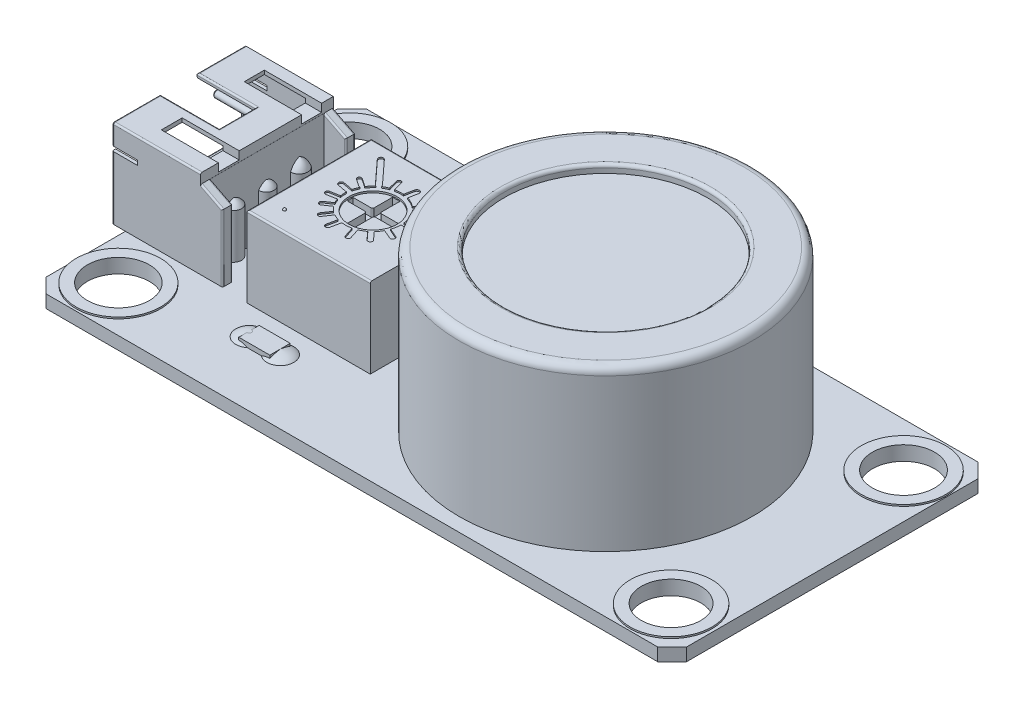
SolidWorks part; units mm, degrees
ref_plane "Alzado" through (0, 0, 0) normal (0, 0, 1) x (1, 0, 0)
ref_plane "Planta" through (0, 0, 0) normal (0, 1, 0) x (1, 0, 0)
ref_plane "Vista lateral" through (0, 0, 0) normal (1, 0, 0) x (0, 0, -1)
sketch "Croquis1" plane through (0, 0, 0) normal (0, 1, 0) x (1, 0, 0)
  line L1 (20, -10) -> (-20, -10)
  line L2 (20, -10) -> (20, 10)
  line L3 (20, 10) -> (-20, 10)
  line L4 (-20, -10) -> (-20, 10)
  line L5 (20, -10) -> (-20, 10) construction
  line L6 (20, 10) -> (-20, -10) construction
  point P0 (0, 0)
  dimension "D1" = 20
  dimension "D2" = 40
extrude "Saliente-Extruir1" add sketch "Croquis1" along normal blind 0.8
chamfer "Chaflán1" distance 0.9 angle 45 4 edges at (20, 0.4, 10) (20, 0.4, -10) (-20, 0.4, -10) (-20, 0.4, 10)
sketch "Croquis2" plane through (0, 0.8, 0) normal (0, 1, 0) x (1, 0, 0)
  circle A0 centre (-17.4865, 7.3544) radius 2.5635
  circle A1 centre (-17.4865, 7.3544) radius 1.8635
  dimension "D1" = 0.7
extrude "Saliente-Extruir2" add sketch "Croquis2" along normal blind 0.1
sketch "Croquis3" plane through (0, 0.8, 0) normal (0, 1, 0) x (1, 0, 0)
  circle A0 centre (-17.3437, -7.2372) radius 2.6343
  circle A2 centre (-17.3437, -7.2372) radius 1.9343
  dimension "D2" = 0.7
extrude "Saliente-Extruir3" add sketch "Croquis3" along normal blind 0.1
sketch "Croquis4" plane through (0, 0.8, 0) normal (0, 1, 0) x (1, 0, 0)
  circle A0 centre (-17.4865, 7.3544) radius 1.8635
extrude "Cortar-Extruir1" cut sketch "Croquis4" against normal through all
sketch "Croquis5" plane through (0, 0.8, 0) normal (0, 1, 0) x (1, 0, 0)
  circle A0 centre (-17.3437, -7.2372) radius 1.9343
extrude "Cortar-Extruir2" cut sketch "Croquis5" against normal through all
sketch "Croquis6" plane through (0, 0.8, 0) normal (0, 1, 0) x (1, 0, 0)
  circle A0 centre (17.306, 7.1429) radius 2.6397
  circle A1 centre (17.306, 7.1429) radius 1.9397
  dimension "D1" = 0.7
extrude "Saliente-Extruir4" add sketch "Croquis6" along normal blind 0.1
sketch "Croquis7" plane through (0, 0.8, 0) normal (0, 1, 0) x (1, 0, 0)
  circle A0 centre (17.306, 7.1429) radius 1.9397
extrude "Cortar-Extruir3" cut sketch "Croquis7" against normal through all
sketch "Croquis8" plane through (0, 0.8, 0) normal (0, 1, 0) x (1, 0, 0)
  circle A0 centre (17.2585, -7.3247) radius 2.5546
  circle A1 centre (17.2585, -7.3247) radius 1.8546
  dimension "D1" = 0.7
extrude "Saliente-Extruir5" add sketch "Croquis8" along normal blind 0.1
sketch "Croquis9" plane through (0, 0.8, 0) normal (0, 1, 0) x (1, 0, 0)
  circle A0 centre (17.2585, -7.3247) radius 1.8546
extrude "Cortar-Extruir4" cut sketch "Croquis9" against normal through all
sketch "Croquis10" plane through (0, 0.8, 0) normal (0, 1, 0) x (1, 0, 0)
  circle A0 centre (5.8533, 0) radius 9.1478
extrude "Saliente-Extruir6" add sketch "Croquis10" along normal blind 10
fillet "Redondeo1" radius 0.5 1 edges at (5.8533, 10.8, 9.1478)
sketch "Croquis11" plane through (0, 10.8, 0) normal (0, 1, 0) x (1, 0, 0)
  circle A1 centre (5.8533, 0) radius 6.3478
extrude "Cortar-Extruir5" cut sketch "Croquis11" against normal blind 0.5
fillet "Redondeo2" radius 0.2 1 edges at (5.8533, 10.8, 6.3478)
sketch "Croquis12" plane through (0, 0.8, 0) normal (0, 1, 0) x (1, 0, 0)
  line L1 (-4.6304, -4.2212) -> (-12.3417, -4.2212)
  line L2 (-4.6304, -4.2212) -> (-4.6304, 3.5532)
  line L3 (-4.6304, 3.5532) -> (-12.3417, 3.5532)
  line L4 (-12.3417, -4.2212) -> (-12.3417, 3.5532)
  line L5 (-4.6304, -4.2212) -> (-12.3417, 3.5532) construction
  line L6 (-4.6304, 3.5532) -> (-12.3417, -4.2212) construction
  point P0 (-8.486, -0.334)
extrude "Saliente-Extruir7" add sketch "Croquis12" along normal blind 5
sketch "Croquis13" plane through (-12.3417, 0, 0) normal (-1, 0, 0) x (0, 0, 1)
  line L0 (-3.2482, 0.8) -> (-3.2482, 5.4444)
  line L1 (-3.5532, 0.8) -> (4.2212, 0.8) construction
  line L2 (-3.2482, 5.4444) -> (-2.7609, 5.4444)
  line L3 (-2.7609, 5.4444) -> (-2.7609, 0.8)
  line L4 (-3.2482, 0.8) -> (-2.7609, 0.8)
  line L5 (-0.2703, 0.8) -> (-0.2703, 5.4444)
  line L6 (-0.2703, 5.4444) -> (0.334, 5.4444)
  line L7 (0.334, 5.4444) -> (0.334, 0.8)
  line L8 (0.334, 0.8) -> (-0.2703, 0.8)
  line L9 (3.8446, 0.8) -> (3.8446, 5.4444)
  line L10 (3.8446, 5.4444) -> (3.213, 5.4444)
  line L11 (3.213, 5.4444) -> (3.213, 0.8)
  line L12 (3.213, 0.8) -> (3.8446, 0.8)
extrude "Cortar-Extruir6" cut sketch "Croquis13" against normal blind 0.5
sketch "Croquis14" plane through (-12.3417, 0, 0) normal (-1, 0, 0) x (0, 0, 1)
  line L0 (0.5209, 0.8) -> (0.5209, 5.4292)
  line L1 (0.334, 0.8) -> (3.213, 0.8) construction
  line L2 (0.5209, 5.4292) -> (0.6837, 5.4292)
  line L3 (0.6837, 5.4292) -> (0.6837, 0.8)
  line L4 (0.6837, 0.8) -> (0.5209, 0.8)
extrude "Cortar-Extruir7" cut sketch "Croquis14" against normal blind 0.5
sketch "Croquis15" plane through (0, 5.8, 0) normal (0, 1, 0) x (1, 0, 0)
  circle A0 centre (-8.486, -0.1934) radius 1.5
  dimension "D1" = 3
extrude "Cortar-Extruir8" cut sketch "Croquis15" against normal blind 0.2
sketch "Croquis16" plane through (0, 5.6, 0) normal (0, 1, 0) x (1, 0, 0)
  line L1 (-8.6131, -1.6051) -> (-8.2995, -1.6051)
  line L3 (-8.2995, 1.2424) -> (-8.6131, 1.2424)
  line L5 (-7.0615, -0.0779) -> (-7.0615, -0.3129)
  line L7 (-9.9142, -0.3129) -> (-9.9142, -0.0779)
  line L12 (-9.9142, -0.0779) -> (-9.9142, 0)
  line L13 (-9.9142, 0) -> (-8.7038, 0)
  line L14 (-8.7038, 0) -> (-8.7038, 1.2424)
  line L15 (-8.6131, 1.2424) -> (-8.7038, 1.2424)
  line L16 (-8.2995, 1.2424) -> (-8.248, 1.2424)
  line L17 (-8.248, 1.2424) -> (-8.248, 0)
  line L18 (-8.248, 0) -> (-7.0615, 0)
  line L19 (-7.0615, 0) -> (-7.0615, -0.0779)
  line L20 (-8.7038, -0.3729) -> (-8.7038, -1.6051)
  line L21 (-8.7038, -1.6051) -> (-8.6131, -1.6051)
  line L22 (-8.2995, -1.6051) -> (-8.248, -1.6051)
  line L23 (-8.248, -1.6051) -> (-8.248, -0.3729)
  line L24 (-9.9142, -0.3129) -> (-9.9142, -0.3729)
  line L25 (-9.9142, -0.3729) -> (-8.7038, -0.3729)
  line L26 (-7.0615, -0.3129) -> (-7.0615, -0.3729)
  line L27 (-7.0615, -0.3729) -> (-8.248, -0.3729)
extrude "Cortar-Extruir9" cut sketch "Croquis16" against normal blind 0.5
sketch "Croquis17" plane through (0, 5.8, 0) normal (0, 1, 0) x (1, 0, 0)
  line L0 (-6.7524, 0) -> (-5.2555, 0)
  line L2 (-5.249, -0.1934) -> (-6.7416, -0.1934)
  line L3 (-6.8257, -0.7476) -> (-6.2758, -0.9833)
  line L4 (-6.9397, -1.0137) -> (-6.3898, -1.2494)
  line L5 (-8.707, -1.9297) -> (-8.8384, -2.5488)
  line L6 (-8.989, -1.8699) -> (-9.1203, -2.489)
  line L8 (-9.3492, -1.7159) -> (-9.6944, -2.2236)
  line L9 (-7.2099, -1.3914) -> (-6.7759, -1.8719)
  line L10 (-7.4236, -1.5844) -> (-6.9895, -2.0649)
  line L11 (-9.5844, -1.5561) -> (-9.9295, -2.0638)
  line L12 (-7.819, -1.8113) -> (-7.6193, -2.4331)
  line L13 (-8.0863, -1.8972) -> (-7.8866, -2.5189)
  line L15 (-9.8499, -1.2901) -> (-10.3142, -1.6052)
  line L16 (-10.0091, -1.0555) -> (-10.4734, -1.3706)
  line L18 (-6.9446, 0.6958) -> (-6.5446, 0.8736)
  line L19 (-6.8207, 0.4171) -> (-6.4207, 0.5949)
  line L21 (-7.3525, 1.1956) -> (-6.9697, 1.5416)
  line L22 (-7.1786, 1.0031) -> (-6.7957, 1.3491)
  line L24 (-10.1981, -0.7928) -> (-10.742, -0.8882)
  line L25 (-10.2482, -0.507) -> (-10.7921, -0.6024)
  line L27 (-10.2774, -0.1035) -> (-10.8548, 0.0057)
  line L28 (-10.2191, 0.2045) -> (-10.7965, 0.3137)
  line L30 (-10.1497, 0.5884) -> (-10.6088, 0.8957)
  line L31 (-10.0059, 0.8032) -> (-10.465, 1.1105)
  line L33 (-9.6996, 1.1667) -> (-11.036, 2.6242)
  line L34 (-9.4691, 1.378) -> (-10.8056, 2.8355)
  line L36 (-9.1158, 1.5096) -> (-9.2471, 2.0302)
  line L37 (-8.8621, 1.5736) -> (-8.9935, 2.0942)
  line L39 (-8.3111, 1.5825) -> (-8.2061, 2.1257)
  line L40 (-7.9859, 1.5196) -> (-7.8808, 2.0628)
  arc A0 (-6.7524, 0) -> (-6.8485, 0.4078) centre (-8.486, -0.1934) ccw
  arc A1 (-5.249, -0.1934) -> (-5.2555, 0) centre (-5.2319, -0.096) ccw
  circle A2 centre (-8.486, -0.1934) radius 1.5
  arc A3 (-6.8257, -0.7476) -> (-6.8312, -0.7453) centre (-6.8827, -0.8806) ccw
  arc A4 (-6.3898, -1.2494) -> (-6.2758, -0.9833) centre (-6.3328, -1.1163) ccw
  arc A5 (-7.8208, -1.806) -> (-7.4274, -1.5799) centre (-8.486, -0.1934) ccw
  arc A6 (-7.214, -1.3871) -> (-6.9452, -1.0112) centre (-8.486, -0.1934) ccw
  arc A7 (-7.2099, -1.3914) -> (-7.214, -1.3871) centre (-7.3167, -1.4879) ccw
  arc A8 (-6.9895, -2.0649) -> (-6.7759, -1.8719) centre (-6.8827, -1.9684) ccw
  arc A9 (-7.819, -1.8113) -> (-7.8208, -1.806) centre (-7.9527, -1.8542) ccw
  arc A10 (-7.8866, -2.5189) -> (-7.6193, -2.4331) centre (-7.753, -2.476) ccw
  arc A11 (-8.0879, -1.8918) -> (-8.0863, -1.8972) centre (-7.9527, -1.8542) ccw
  arc A12 (-7.4274, -1.5799) -> (-7.4236, -1.5844) centre (-7.3167, -1.4879) ccw
  arc A13 (-6.9452, -1.0112) -> (-6.9397, -1.0137) centre (-6.8827, -0.8806) ccw
  arc A14 (-6.8312, -0.7453) -> (-6.7416, -0.1934) centre (-8.486, -0.1934) ccw
  arc A15 (-8.707, -1.9297) -> (-8.7059, -1.9239) centre (-8.848, -1.8998) ccw
  arc A16 (-9.1203, -2.489) -> (-8.8384, -2.5488) centre (-8.9793, -2.5189) ccw
  arc A17 (-9.3492, -1.7159) -> (-9.346, -1.7111) centre (-9.4668, -1.636) ccw
  arc A18 (-9.9295, -2.0638) -> (-9.6944, -2.2236) centre (-9.8119, -2.1437) ccw
  arc A19 (-9.8499, -1.2901) -> (-9.8452, -1.2868) centre (-9.9295, -1.1728) ccw
  arc A20 (-10.4734, -1.3706) -> (-10.3142, -1.6052) centre (-10.3938, -1.4879) ccw
  arc A21 (-6.9446, 0.6958) -> (-6.9748, 0.678) centre (-6.8827, 0.5564) ccw
  arc A22 (-6.4207, 0.5949) -> (-6.5446, 0.8736) centre (-6.4826, 0.7343) ccw
  arc A23 (-7.3525, 1.1956) -> (-7.3817, 1.157) centre (-7.2655, 1.0994) ccw
  arc A24 (-6.7957, 1.3491) -> (-6.9697, 1.5416) centre (-6.8827, 1.4454) ccw
  arc A25 (-10.1981, -0.7928) -> (-10.1343, -0.7646) centre (-10.2232, -0.6499) ccw
  arc A26 (-10.7921, -0.6024) -> (-10.742, -0.8882) centre (-10.7671, -0.7453) ccw
  arc A27 (-10.2774, -0.1035) -> (-10.2282, -0.105) centre (-10.2482, 0.0505) ccw
  arc A28 (-10.7965, 0.3137) -> (-10.8548, 0.0057) centre (-10.8256, 0.1597) ccw
  arc A29 (-10.1497, 0.5884) -> (-10.0553, 0.5686) centre (-10.0778, 0.6958) ccw
  arc A30 (-10.465, 1.1105) -> (-10.6088, 0.8957) centre (-10.5369, 1.0031) ccw
  arc A31 (-9.6996, 1.1667) -> (-9.6306, 1.123) centre (-9.5844, 1.2724) ccw
  arc A32 (-10.8056, 2.8355) -> (-11.036, 2.6242) centre (-10.9208, 2.7299) ccw
  arc A33 (-9.1158, 1.5096) -> (-9.0794, 1.4471) centre (-8.989, 1.5416) ccw
  arc A34 (-8.9935, 2.0942) -> (-9.2471, 2.0302) centre (-9.1203, 2.0622) ccw
  arc A35 (-8.3111, 1.5825) -> (-8.3139, 1.5425) centre (-8.1485, 1.5511) ccw
  arc A36 (-7.8808, 2.0628) -> (-8.2061, 2.1257) centre (-8.0435, 2.0942) ccw
  arc A37 (-6.8485, 0.4078) -> (-6.8207, 0.4171) centre (-6.8827, 0.5564) ccw
  arc A38 (-6.9748, 0.678) -> (-7.2013, 0.9867) centre (-8.486, -0.1934) ccw
  arc A39 (-7.2013, 0.9867) -> (-7.1786, 1.0031) centre (-7.2655, 1.0994) ccw
  arc A40 (-7.3817, 1.157) -> (-7.9982, 1.4815) centre (-8.486, -0.1934) ccw
  arc A41 (-7.9982, 1.4815) -> (-7.9859, 1.5196) centre (-8.1485, 1.5511) ccw
  arc A42 (-8.3139, 1.5425) -> (-8.862, 1.5101) centre (-8.486, -0.1934) ccw
  arc A43 (-8.862, 1.5101) -> (-8.8621, 1.5736) centre (-8.989, 1.5416) ccw
  arc A44 (-9.0794, 1.4471) -> (-9.4281, 1.2748) centre (-8.486, -0.1934) ccw
  arc A45 (-9.4281, 1.2748) -> (-9.4691, 1.378) centre (-9.5844, 1.2724) ccw
  arc A46 (-9.6306, 1.123) -> (-9.9576, 0.7434) centre (-8.486, -0.1934) ccw
  arc A47 (-9.9576, 0.7434) -> (-10.0059, 0.8032) centre (-10.0778, 0.6958) ccw
  arc A48 (-10.0553, 0.5686) -> (-10.1868, 0.1947) centre (-8.486, -0.1934) ccw
  arc A49 (-10.1868, 0.1947) -> (-10.2191, 0.2045) centre (-10.2482, 0.0505) ccw
  arc A50 (-10.2282, -0.105) -> (-10.2021, -0.5064) centre (-8.486, -0.1934) ccw
  arc A51 (-10.2021, -0.5064) -> (-10.2482, -0.507) centre (-10.2232, -0.6499) ccw
  arc A52 (-10.1343, -0.7646) -> (-10.0043, -1.0524) centre (-8.486, -0.1934) ccw
  arc A53 (-10.0043, -1.0524) -> (-10.0091, -1.0555) centre (-9.9295, -1.1728) ccw
  arc A54 (-9.8452, -1.2868) -> (-9.581, -1.5513) centre (-8.486, -0.1934) ccw
  arc A55 (-9.581, -1.5513) -> (-9.5844, -1.5561) centre (-9.4668, -1.636) ccw
  arc A56 (-9.346, -1.7111) -> (-8.9876, -1.8641) centre (-8.486, -0.1934) ccw
  arc A57 (-8.9876, -1.8641) -> (-8.989, -1.8699) centre (-8.848, -1.8998) ccw
  arc A58 (-8.7059, -1.9239) -> (-8.0879, -1.8918) centre (-8.486, -0.1934) ccw
  point P11 (-6.6078, -0.9985)
  point P18 (2.9909, -1.5468)
  point P19 (-8.9137, -2.2094)
  point P25 (-7.0997, -1.7281)
  point P32 (-7.8528, -2.1651)
  point P46 (-9.6394, -1.8898)
  point P53 (-10.1617, -1.3304)
  point P60 (-6.6827, 0.6453)
  point P67 (-7.0741, 1.2724)
  point P74 (-10.4951, -0.6976)
  point P81 (-10.5369, 0.1051)
  point P88 (-10.3074, 0.8495)
  point P95 (-10.2526, 2.0011)
  point P102 (-9.0546, 1.8019)
  point P109 (-8.096, 1.8226)
extrude "Cortar-Extruir10" cut sketch "Croquis17" against normal blind 0.09
fillet "Redondeo3" radius 0.1 3 edges at (-8.486, 5.8, -3.5532) (-12.3417, 5.8, 0.334) (-8.486, 5.8, 4.2212)
fillet "Redondeo4" radius 0.1 4 edges at (-8.7038, 5.35, 0.3729) (-8.248, 5.35, 0.3729) (-8.7038, 5.35, 0) (-8.248, 5.35, 0)
sketch "Croquis18" plane through (0, 5.8, 0) normal (0, 1, 0) x (1, 0, 0)
  line L0 (-11.2871, -3.0045) -> (-11.1022, -3.0045)
  arc A0 (-11.1022, -3.0045) -> (-11.2871, -3.0045) centre (-11.1947, -3.0045) ccw
revolve "Revolución1" add sketch "Croquis18" angle 360 about L0
sketch "Croquis19" plane through (0, 0.8, 0) normal (0, 1, 0) x (1, 0, 0)
  line L1 (-8.4965, -6.6295) -> (-10.4343, -6.6295)
  line L2 (-8.4965, -6.6295) -> (-8.4965, -5.3534)
  line L3 (-8.4965, -5.3534) -> (-10.4343, -5.3534)
  line L4 (-10.4343, -6.6295) -> (-10.4343, -5.3534)
  line L5 (-8.4965, -6.6295) -> (-10.4343, -5.3534) construction
  line L6 (-8.4965, -5.3534) -> (-10.4343, -6.6295) construction
  point P0 (-9.4654, -5.9914)
extrude "Saliente-Extruir8" add sketch "Croquis19" along normal blind 0.3
ref_plane "Plano1" through (0, 0, 5.97) normal (0, 0, 1) x (1, 0, 0)
sketch "Croquis20" plane through (0, 0, 5.97) normal (0, 0, 1) x (1, 0, 0)
  line L0 (-8.4965, 1.1) -> (-8.4965, 0.8)
  line L1 (-8.4965, 0.8) -> (-7.6501, 0.8)
  spline S0 degree 3 poles (-8.4965, 1.1) (-8.2056, 1.0412) (-7.8872, 0.9962) (-7.6501, 0.8) knots 0 0 0 0 1 1 1 1
revolve "Revolución2" add sketch "Croquis20" angle 360 about L0
sketch "Croquis21" plane through (0, 0, 5.97) normal (0, 0, 1) x (1, 0, 0)
  line L0 (-10.4343, 1.1) -> (-10.4343, 0.8)
  line L1 (-10.4343, 1.1) -> (-10.4343, 0.8) construction
  line L2 (-10.4343, 0.8) -> (-11.22, 0.8)
  line L4 (-11.22, 0.8) -> (-11.2803, 0.8)
  spline S0 degree 2 poles (-10.4343, 1.1) (-10.9186, 1.1271) (-11.2803, 0.8) knots 0 0 0 1 1 1
revolve "Revolución3" add sketch "Croquis21" angle 360 about L0
sketch "Croquis22" plane through (0, 0.8, 0) normal (0, 1, 0) x (1, 0, 0)
  line L1 (-13.9306, 4.1401) -> (-21.6418, 4.1401)
  line L2 (-13.9306, 4.1401) -> (-13.9306, -4.1401)
  line L3 (-13.9306, -4.1401) -> (-21.6418, -4.1401)
  line L4 (-21.6418, 4.1401) -> (-21.6418, -4.1401)
  line L5 (-13.9306, 4.1401) -> (-21.6418, -4.1401) construction
  line L6 (-13.9306, -4.1401) -> (-21.6418, 4.1401) construction
  point P0 (-17.7862, 0)
extrude "Saliente-Extruir9" add sketch "Croquis22" along normal blind 5.5
sketch "Croquis23" plane through (0, 6.3, 0) normal (0, 1, 0) x (1, 0, 0)
  line L0 (-13.9306, 3.5583) -> (-15.2997, 3.5583)
  line L1 (-13.9306, -4.1401) -> (-13.9306, 4.1401) construction
  line L3 (-13.9306, 3.5583) -> (-13.9306, -3.5217)
  line L4 (-13.9306, -4.1401) -> (-13.9306, 4.1401) construction
  line L5 (-13.9306, -3.5217) -> (-15.2997, -3.5217)
  line L6 (-15.2997, 3.5583) -> (-15.2997, -3.5217)
extrude "Cortar-Extruir11" cut sketch "Croquis23" against normal blind 5.5
sketch "Croquis24" plane through (0, 0, 4.1401) normal (0, 0, 1) x (1, 0, 0)
  line L0 (-15.3022, 6.3) -> (-15.3022, 5.6849)
  line L1 (-21.6418, 6.3) -> (-13.9306, 6.3) construction
  line L2 (-15.3022, 5.6849) -> (-13.9306, 4.9885)
  line L3 (-13.9306, 6.3) -> (-13.9306, 0.8) construction
  line L4 (-13.9306, 4.9885) -> (-13.9306, 6.3)
  line L5 (-13.9306, 6.3) -> (-15.3022, 6.3)
extrude "Cortar-Extruir12" cut sketch "Croquis24" against normal blind 9.5
sketch "Croquis25" plane through (0, 0, 4.1401) normal (0, 0, 1) x (1, 0, 0)
  line L0 (-20.8209, 6.3) -> (-21.6418, 6.3)
  line L1 (-21.6418, 6.3) -> (-15.3022, 6.3) construction
  line L2 (-21.6418, 6.3) -> (-21.6418, 0.8)
  line L3 (-21.6418, 0.8) -> (-20.8209, 0.8)
  line L4 (-21.6418, 0.8) -> (-20, 0.8) construction
  line L5 (-20.8209, 0.8) -> (-20.8209, 6.3)
extrude "Cortar-Extruir13" cut sketch "Croquis25" against normal blind 9.5
ref_plane "Plano2" through (0, 0, 2.0901) normal (0, 0, 1) x (1, 0, 0)
ref_plane "Plano3" through (0, 0, 0.0401) normal (0, 0, 1) x (1, 0, 0)
ref_plane "Plano4" through (0, 0, -2.0099) normal (0, 0, 1) x (1, 0, 0)
sketch "Croquis27" plane through (0, 0, 2.0901) normal (0, 0, 1) x (1, 0, 0)
  line L0 (-15.3022, 3.95) -> (-15.3022, 0.8)
  line L1 (-19.1, 0.8) -> (19.1, 0.8) construction
  line L2 (-15.3022, 0.8) -> (-14.8012, 0.8)
  line L3 (-14.8012, 0.8) -> (-14.8012, 3.6)
  spline S0 degree 2 poles (-14.8012, 3.6) (-15.0016, 3.849) (-15.3022, 3.95) knots 0 0 0 1 1 1
  dimension "D1" = 2.8
revolve "Revolución4" add sketch "Croquis27" angle 360 about L0
sketch "Croquis28" plane through (0, 0, 0.0401) normal (0, 0, 1) x (1, 0, 0)
  line L0 (-15.3022, 3.8932) -> (-15.3022, 0.8)
  line L1 (-19.1, 0.8) -> (19.1, 0.8) construction
  line L2 (-15.3022, 0.8) -> (-14.825, 0.8)
  line L3 (-14.825, 0.8) -> (-14.825, 3.55)
  spline S0 degree 2 poles (-14.825, 3.55) (-14.9932, 3.8261) (-15.3022, 3.8932) knots 0 0 0 1 1 1
revolve "Revolución5" add sketch "Croquis28" angle 360 about L0
sketch "Croquis29" plane through (0, 0, -2.0099) normal (0, 0, 1) x (1, 0, 0)
  line L0 (-15.3022, 4.1143) -> (-15.3022, 0.8)
  line L1 (-19.1, 0.8) -> (19.1, 0.8) construction
  line L2 (-15.3022, 0.8) -> (-14.7641, 0.8)
  line L3 (-14.7641, 0.8) -> (-14.7641, 3.55)
  spline S0 degree 2 poles (-14.7641, 3.55) (-14.9211, 3.9482) (-15.3022, 4.1143) knots 0 0 0 1 1 1
revolve "Revolución6" add sketch "Croquis29" angle 360 about L0
sketch "Croquis30" plane through (-20.8209, 0, 0) normal (-1, 0, 0) x (0, 0, 1)
  line L0 (-3.5712, 0.8) -> (-3.5712, 1.2659)
  line L1 (-4.1401, 0.8) -> (4.1401, 0.8) construction
  line L2 (-3.5712, 1.2659) -> (3.5217, 1.2659)
  line L3 (3.5217, 1.2659) -> (3.5217, 0.8)
  line L4 (3.5217, 0.8) -> (-3.5712, 0.8)
extrude "Cortar-Extruir14" cut sketch "Croquis30" against normal blind 4.5
sketch "Croquis31" plane through (-20.8209, 0, 0) normal (-1, 0, 0) x (0, 0, 1)
  line L0 (-3.9344, 6.0631) -> (-3.9344, 1.4969)
  line L1 (-3.9344, 1.4969) -> (3.8803, 1.4969)
  line L3 (3.8803, 6.0631) -> (-3.9344, 6.0631)
  line L4 (3.8803, 6.0631) -> (3.9314, 6.0631)
  line L5 (3.9314, 6.0631) -> (3.9314, 1.4969)
  line L6 (3.9314, 1.4969) -> (3.8803, 1.4969)
extrude "Cortar-Extruir15" cut sketch "Croquis31" against normal blind 4.5
sketch "Croquis32" plane through (0, 0, 4.1401) normal (0, 0, 1) x (1, 0, 0)
  line L0 (-20.8209, 4.7386) -> (-19.2416, 4.7386)
  line L1 (-20.8209, 0.8) -> (-20.8209, 6.3) construction
  line L2 (-19.2416, 4.7386) -> (-19.2416, 5.0288)
  line L3 (-19.2416, 5.0288) -> (-20.8209, 5.0288)
  line L4 (-20.8209, 5.0288) -> (-20.8209, 4.7386)
extrude "Cortar-Extruir16" cut sketch "Croquis32" against normal blind 11.5
sketch "Croquis33" plane through (0, 6.3, 0) normal (0, 1, 0) x (1, 0, 0)
  line L1 (-17.1372, -1.1413) -> (-22.0732, -1.1413)
  line L2 (-17.1372, -1.1413) -> (-17.1372, 1.1413)
  line L3 (-17.1372, 1.1413) -> (-22.0732, 1.1413)
  line L4 (-22.0732, -1.1413) -> (-22.0732, 1.1413)
  line L5 (-17.1372, -1.1413) -> (-22.0732, 1.1413) construction
  line L6 (-17.1372, 1.1413) -> (-22.0732, -1.1413) construction
  point P0 (-19.6052, 0)
extrude "Cortar-Extruir17" cut sketch "Croquis33" against normal blind 3.5
sketch "Croquis34" plane through (0, 6.3, 0) normal (0, 1, 0) x (1, 0, 0)
  line L1 (-14.9619, 3.4134) -> (-18.8796, 3.4134)
  line L2 (-14.9619, 3.4134) -> (-14.9619, 2.1629)
  line L3 (-14.9619, 2.1629) -> (-18.8796, 2.1629)
  line L4 (-18.8796, 3.4134) -> (-18.8796, 2.1629)
  line L5 (-14.9619, 3.4134) -> (-18.8796, 2.1629) construction
  line L6 (-14.9619, 2.1629) -> (-18.8796, 3.4134) construction
  point P0 (-16.9207, 2.7882)
  dimension "D1" = 1.2505
extrude "Cortar-Extruir18" cut sketch "Croquis34" against normal blind 0.5
sketch "Croquis35" plane through (0, 6.3, 0) normal (0, 1, 0) x (1, 0, 0)
  line L1 (-13.7253, -1.7333) -> (-18.8618, -1.7333)
  line L2 (-13.7253, -1.7333) -> (-13.7253, -3.0333)
  line L3 (-13.7253, -3.0333) -> (-18.8618, -3.0333)
  line L4 (-18.8618, -1.7333) -> (-18.8618, -3.0333)
  line L5 (-13.7253, -1.7333) -> (-18.8618, -3.0333) construction
  line L6 (-13.7253, -3.0333) -> (-18.8618, -1.7333) construction
  point P0 (-16.2936, -2.3833)
  dimension "D1" = 1.3
extrude "Cortar-Extruir19" cut sketch "Croquis35" against normal blind 0.5
fillet "Redondeo5" radius 0.1 14 edges at (-20.8209, 5.6644, -4.1401) (-20.8209, 2.7693, -4.1401) (-20.8209, 5.6644, 4.1401) (-20.8209, 2.7693, 4.1401) (-18.0616, 6.3, 4.1401) (-18.979, 6.3, 1.1413) (-17.1372, 6.3, 0) (-18.979, 6.3, -1.1413) (-20.8209, 6.0631, -2.5379) (-20.8209, 6.0631, 2.5364) (-20.8209, 6.3, 2.6407) (-20.8209, 6.3, -2.6407) (-20.8209, 1.2659, -0.0247) (-20.8209, 1.4969, -0.0015)
fillet "Redondeo6" radius 0.1 8 edges at (-13.9306, 2.8943, -3.5583) (-14.6151, 5.3361, -3.5583) (-14.6164, 5.3367, -4.1401) (-13.9306, 2.8943, -4.1401) (-13.9306, 2.8943, 3.5217) (-14.6151, 5.3361, 3.5217) (-13.9306, 2.8943, 4.1401) (-14.6164, 5.3367, 4.1401)
sketch "Croquis36" plane through (-16.3209, 0, 0) normal (-1, 0, 0) x (0, 0, 1)
  circle A0 centre (0, 4.6367) radius 0.2129
  circle A1 centre (-2.3317, 4.6367) radius 0.2129
  circle A2 centre (2.4319, 4.6367) radius 0.2129
extrude "Saliente-Extruir10" add sketch "Croquis36" along normal blind 4.5
fillet "Redondeo7" radius 0.1 3 edges at (-20.8209, 4.6367, 2.6448) (-20.8209, 4.6367, 0.2129) (-20.8209, 4.6367, -2.1188)
